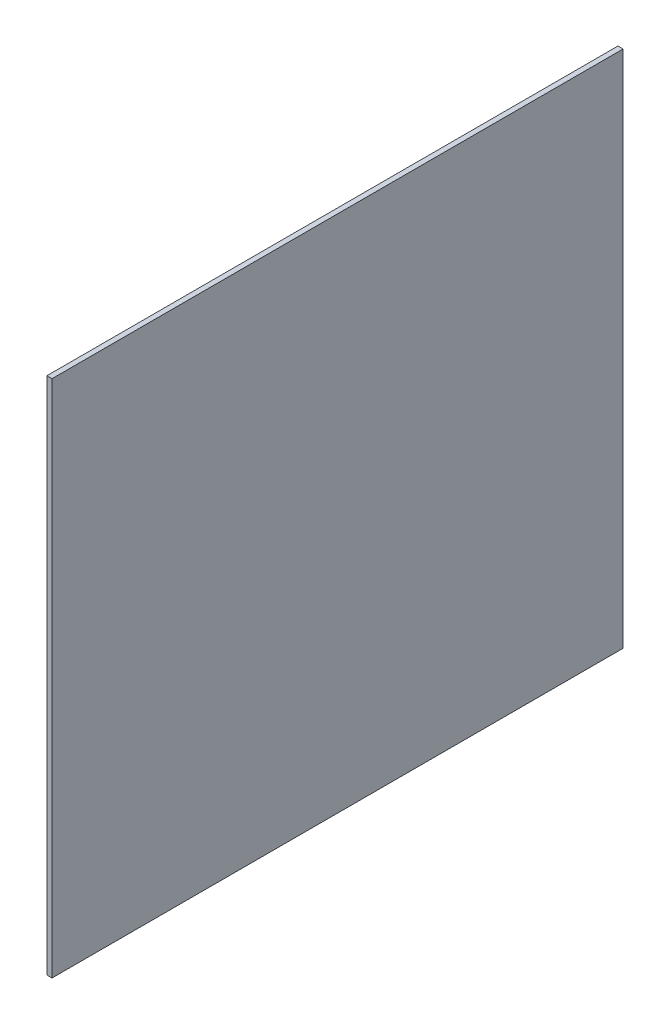
SolidWorks part; units mm, degrees
ref_plane "Front Plane" through (0, 0, 0) normal (0, 0, 1) x (1, 0, 0)
ref_plane "Top Plane" through (0, 0, 0) normal (0, 1, 0) x (1, 0, 0)
ref_plane "Right Plane" through (0, 0, 0) normal (1, 0, 0) x (0, 0, -1)
sketch "Sketch1" plane through (0, 0, 0) normal (0, 0, 1) x (1, 0, 0)
  line L0 (0, 0) -> (0, -150.8811) construction
  line L1 (0, -150.8811) -> (150.8811, -150.8811) construction
  line L2 (150.8811, -150.8811) -> (150.8811, 0) construction
  line L3 (150.8811, -140.8811) -> (150.8811, 0)
  line L4 (150.8811, 0) -> (152.2755, 0)
  line L5 (152.2755, 0) -> (152.2755, -140.8811)
  line L7 (150.8811, -140.8811) -> (152.2755, -140.8811)
  circle A0 centre (0, 0) radius 150.8811 construction
  dimension "D1" = 301.7622
  dimension "D2" = 1.3945
  dimension "D3" = 10
extrude "Boss-Extrude1" add sketch "Sketch1" along normal blind 155
